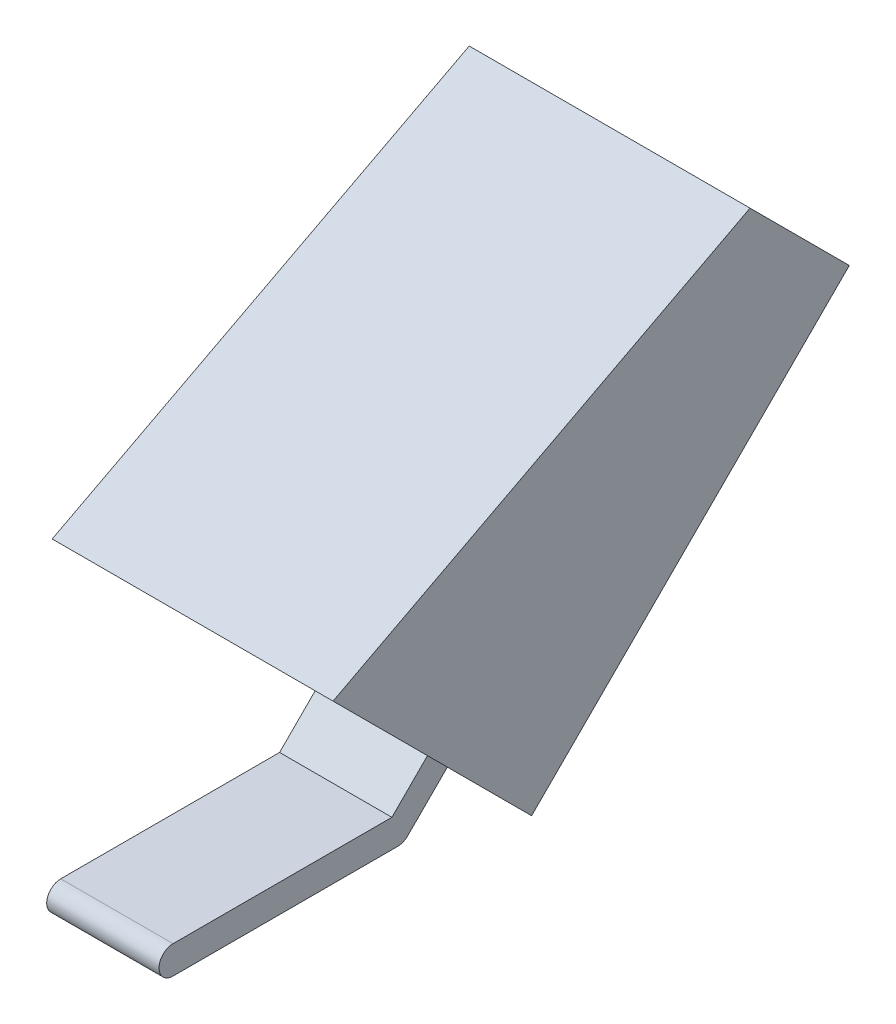
SolidWorks part; units mm, degrees
ref_plane "Front" through (0, 0, 0) normal (0, 0, 1) x (1, 0, 0)
ref_plane "Top" through (0, 0, 0) normal (0, 1, 0) x (1, 0, 0)
ref_plane "Right" through (0, 0, 0) normal (1, 0, 0) x (0, 0, -1)
sketch "草图1" plane through (0, 0, 0) normal (1, 0, 0) x (0, 0, -1)
  line L0 (-8, 0) -> (8, 0) construction
  line L1 (-8, 1) -> (7.5858, 1)
  line L2 (-8, -1) -> (8, -1)
  line L3 (8, 0) -> (24.1742, 16.1742) construction
  line L4 (8, 0) -> (27.799, 19.799) construction
  line L5 (7.5858, 1) -> (27.0919, 20.5061)
  line L6 (8.7071, -0.7071) -> (28.5061, 19.0919)
  arc A0 (-8, 1) -> (-8, -1) centre (-8, 0) ccw
  arc A1 (8, -1) -> (8.7071, -0.7071) centre (8, 0) ccw
  arc A2 (8, -1) -> (8.7071, -0.7071) centre (8, 0) ccw
  arc A3 (28.5061, 19.0919) -> (27.0919, 20.5061) centre (27.799, 19.799) ccw
  point P2 (0, 0)
  point P11 (17.8995, 9.8995)
  dimension "D1" = 135
extrude "凸台-拉伸2" add sketch "草图1" along normal mid plane 8 contours L6 A3 L5 L1 A1 | A2 L5 L1 A0 L2 region at (0, 0.5637, 0.2071)
sketch "草图5" plane through (0, -4.7071, -4.7071) normal (0, -0.7071, -0.7071) x (1, 0, 0)
  line L0 (0, -5.6569) -> (0, -36.6143) construction
  line L1 (4, -5.6569) -> (-4, -5.6569) construction
  line L3 (-10, -9.6569) -> (10, -9.6569)
  line L4 (-10, -9.6569) -> (-10, -41.6569)
  line L5 (-10, -41.6569) -> (10, -41.6569)
  line L6 (10, -9.6569) -> (10, -41.6569)
  dimension "D1" = 4
  dimension "D2" = 32
  dimension "D3" = 20
  dimension "D4" = 10
extrude "凸台-拉伸5" add sketch "草图5" against normal blind 20
sketch "草图6" plane through (-10, 0, 0) normal (-1, 0, 0) x (0, 0, 1)
  line L0 (2.6066, 16.2635) -> (-27.0919, 31.8198)
  line L1 (-20.0208, 38.8909) -> (-34.163, 24.7487) construction
  line L2 (-27.0919, 31.8198) -> (-20.0208, 38.8909)
  line L3 (-20.0208, 38.8909) -> (2.6066, 16.2635)
extrude "切除-拉伸3" cut sketch "草图6" against normal blind 20
